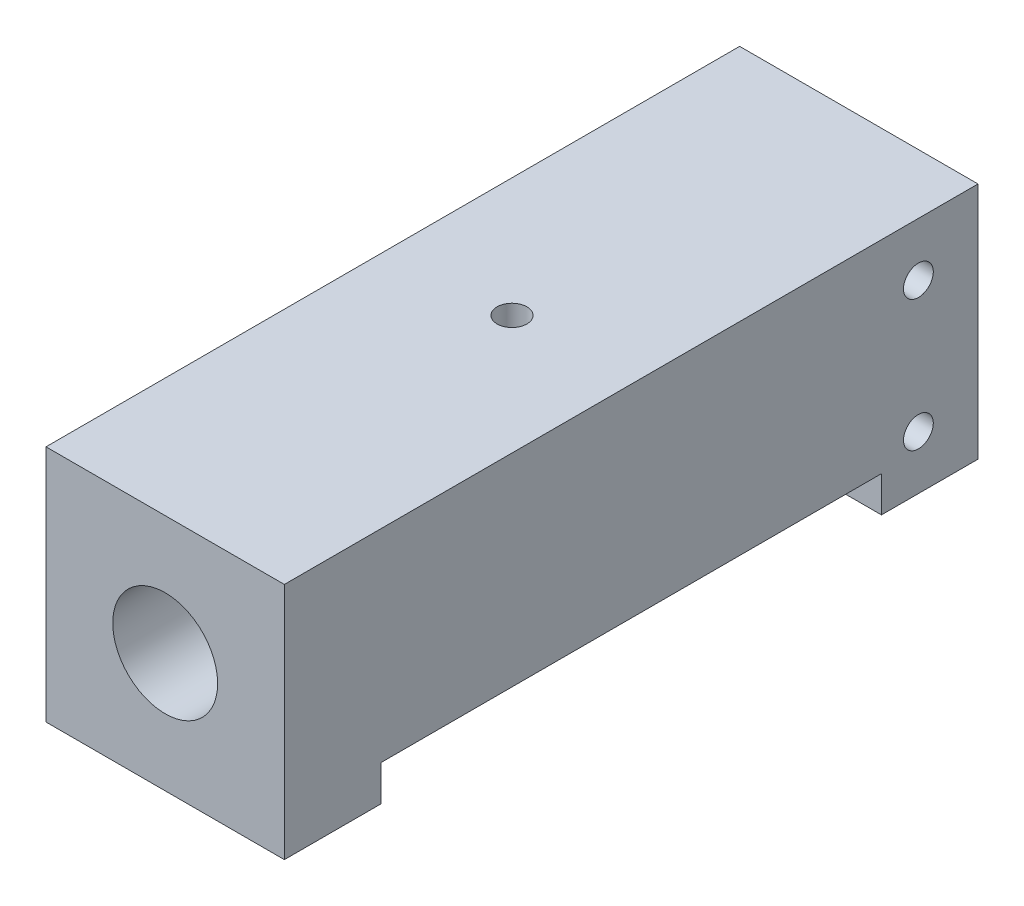
SolidWorks part; units mm, degrees
material "6063-T5"
ref_plane "Piano frontale" through (0, 0, 0) normal (0, 0, 1) x (1, 0, 0)
ref_plane "Piano superiore" through (0, 0, 0) normal (0, 1, 0) x (1, 0, 0)
ref_plane "Piano destro" through (0, 0, 0) normal (1, 0, 0) x (0, 0, -1)
sketch "Schizzo1" plane through (0, 0, 0) normal (0, 0, 1) x (1, 0, 0)
  line L1 (10, -10) -> (-10, -10)
  line L2 (10, -10) -> (10, 10)
  line L3 (10, 10) -> (-10, 10)
  line L4 (-10, -10) -> (-10, 10)
  line L5 (10, -10) -> (-10, 10) construction
  line L6 (10, 10) -> (-10, -10) construction
  point P0 (0, 0)
  dimension "D1" = 20
  dimension "D2" = 20
extrude "Estrusione-Estrusione1" add sketch "Schizzo1" against normal blind 58.2
sketch "Schizzo2" plane through (0, 0, -58.2) normal (0, 0, -1) x (-1, 0, 0)
  circle A0 centre (0, 0) radius 2.05
  dimension "D1" = 4.1
extrude "Taglio-Estrusione1" cut sketch "Schizzo2" against normal through all
sketch "Schizzo3" plane through (0, 0, -58.2) normal (0, 0, -1) x (-1, 0, 0)
  point P0 (0, 0)
hole_wizard "Foro filettato G1/8-1" positions "Schizzo8" profile "Schizzo7" tap size "G1/8" standard "BSI"
sketch "Schizzo8" plane through (0, 0, 0) normal (0, 0, 1) x (1, 0, 0)
  point P0 (0, 0)
sketch "Schizzo7" plane through (0, 0, 0) normal (1, 0, 0) x (0, -1, 0)
  line L0 (0, 0) -> (0, 12.6438)
  line L1 (0, 12.6438) -> (4.4, 10)
  line L2 (4.4, 10) -> (4.4, 0)
  line L5 (4.4, 0) -> (0, 0)
  line L10 (0, 12.6438) -> (-4.4, 10) construction
  line L11 (0, -6.35) -> (0, 107.95) construction
  dimension "Tap Drill Dia." = 8.8
  dimension "Tap Drill Depth" = 10
  dimension "Drill Angle" = 118
sketch "Schizzo11" plane through (0, 10, 0) normal (0, 1, 0) x (1, 0, 0)
  line L0 (0, 58.2) -> (0, 0) construction
  line L1 (10, 58.2) -> (-10, 58.2) construction
  line L2 (10, 29.1) -> (-10, 29.1) construction
  line L3 (10, 58.2) -> (10, 0) construction
  point P10 (0, 29.1)
  point P11 (0, 29.1)
  point P12 (0, 29.1)
hole_wizard "M3 Tapped Hole2" positions "Schizzo3D1" profile "Schizzo12" tap size "M3" standard "DIN"
sketch3d "Schizzo3D1"
  point P0 (0, 10, -29.1)
sketch "Schizzo12" plane through (0, 10, -29.1) normal (1, 0, 0) x (0, 0, 1)
  line L0 (0, 0) -> (0, 5.7511)
  line L1 (0, 5.7511) -> (1.25, 5)
  line L2 (1.25, 5) -> (1.25, 0)
  line L5 (1.25, 0) -> (0, 0)
  line L10 (0, 5.7511) -> (-1.25, 5) construction
  line L11 (0, -6.35) -> (0, 107.95) construction
  dimension "Tap Drill Dia." = 2.5
  dimension "Tap Drill Depth" = 5
  dimension "Drill Angle" = 118
cosmetic thread "Hole Thread4" parameters "D1"=5, "D2"=3
hole_wizard "Foro Ø16.0 (16)-1" positions "Schizzo3D3" profile "Schizzo14" hole size "Ø16.0" standard "ISO"
sketch3d "Schizzo3D3"
  point P0 (0, 0, 0)
  point P3 (0, 0, -58.2)
sketch "Schizzo14" plane through (0, 0, -58.2) normal (1, 0, 0) x (0, 1, 0)
  line L0 (0, 0) -> (0, 16.8069)
  line L1 (0, 16.8069) -> (8, 12)
  line L2 (8, 12) -> (8, 0)
  line L5 (8, 0) -> (0, 0)
  line L10 (0, 16.8069) -> (-8, 12) construction
  line L11 (0, -6.35) -> (0, 107.95) construction
  dimension "Hole Dia." = 16
  dimension "Hole Depth" = 12
  dimension "Drill Angle" = 118
sketch "Schizzo15" plane through (10, 0, 0) normal (1, 0, 0) x (0, 0, -1)
  line L0 (46.2, 0) -> (58.2, 0) construction
  line L1 (46.2, 8) -> (46.2, -8) construction
  line L4 (58.2, -10) -> (58.2, 10) construction
  line L6 (58.2, -10) -> (0, -10) construction
  point P5 (53.2, -5.5)
  point P8 (53.2, 5.5)
  dimension "D1" = 5.5
  dimension "D2" = 7
  dimension "D3" = 5
  dimension "D4" = 4.5
hole_wizard "M3 Tapped Hole3" positions "Schizzo3D4" profile "Schizzo16" tap size "M3" standard "ISO" end condition up to next
sketch3d "Schizzo3D4"
  point P0 (10, 5.5, -53.2)
  point P3 (10, -5.5, -53.2)
sketch "Schizzo16" plane through (10, 5.5, -53.2) normal (0, 1, 0) x (0, 0, -1)
  line L0 (0, 0) -> (0, 4.1905)
  line L1 (0, 4.1905) -> (1.25, 4.1905)
  line L2 (1.25, 4.1905) -> (1.25, 0)
  line L5 (1.25, 0) -> (0, 0)
  line L11 (0, -6.35) -> (0, 107.95) construction
  dimension "Thread Major Dia." = 2.5
  dimension "Thru Tap Drill Depth" = 4.1905
sketch "Sketch1" plane through (-10, 0, 0) normal (-1, 0, 0) x (0, 0, 1)
  line L0 (-58.2, 10) -> (-58.2, -10) construction
  line L1 (-58.2, 3) -> (-22, 3)
  line L2 (-58.2, 3) -> (-58.2, -3)
  line L3 (-58.2, -3) -> (-22, -3)
  line L4 (-22, 3) -> (-22, -3)
  line L5 (0, 10) -> (0, -10) construction
  line L6 (0, 0) -> (-22, 0) construction
  point P8 (-22, 0)
  dimension "D1" = 6
  dimension "D2" = 22
extrude "Boss-Extrude1" add sketch "Sketch1" along normal blind 4.9
sketch "Sketch2" plane through (10, 0, 0) normal (1, 0, 0) x (0, 0, -1)
  line L0 (58.2, -10) -> (0, -10) construction
  line L1 (50.1, -10) -> (34.1, -10)
  line L2 (50.1, -10) -> (50.1, -7)
  line L3 (50.1, -7) -> (34.1, -7)
  line L4 (34.1, -7) -> (8.1, -7)
  line L5 (42.1, -7) -> (42.1, -12.5) construction
  line L6 (8.1, -7) -> (8.1, -10)
  line L7 (8.1, -10) -> (34.1, -10)
  line L8 (0, -10) -> (8.1, -10) construction
  line L9 (50.1, -10) -> (58.2, -10) construction
  dimension "D1" = 16
  dimension "D2" = 3
extrude "Cut-Extrude1" cut sketch "Sketch2" against normal through all
sketch "Sketch3" plane through (0, 0, -22) normal (0, 0, 1) x (1, 0, 0)
  point P0 (-13, 0)
hole_wizard "M3 Tapped Hole4" positions "Sketch6" profile "Sketch7" tap size "M3" standard "ISO"
sketch "Sketch6" plane through (0, 0, -22) normal (0, 0, 1) x (1, 0, 0)
  point P0 (-13, 0)
sketch "Sketch7" plane through (-13, 0, -22) normal (1, 0, 0) x (0, -1, 0)
  line L0 (0, 0) -> (0, 20.7511)
  line L1 (0, 20.7511) -> (1.25, 20)
  line L2 (1.25, 20) -> (1.25, 0)
  line L5 (1.25, 0) -> (0, 0)
  line L10 (0, 20.7511) -> (-1.25, 20) construction
  line L11 (0, -6.35) -> (0, 107.95) construction
  dimension "Tap Drill Dia." = 2.5
  dimension "Tap Drill Depth" = 20
  dimension "Drill Angle" = 118
sketch "Sketch8" plane through (-10, 0, 0) normal (-1, 0, 0) x (0, 0, 1)
  line L1 (0, 10) -> (-58.2, 10) construction
  line L2 (0, 10) -> (0, -10) construction
  line L3 (0, -10) -> (-58.2, -10) construction
  line L4 (-58.2, 10) -> (-58.2, -10) construction
sketch "Sketch9" plane through (0, -10, 0) normal (0, -1, 0) x (1, 0, 0)
  line L1 (14, -8.1) -> (-14, -8.1) construction
  line L2 (14, -8.1) -> (14, -50.1) construction
  line L3 (14, -50.1) -> (-14, -50.1) construction
  line L4 (-14, -8.1) -> (-14, -50.1) construction
  line L6 (-10, -50.1) -> (-3.873, -50.1) construction
  line L7 (-10, -8.1) -> (10, -8.1) construction
  line L8 (10, -50.1) -> (10, -8.1) construction
  line L9 (-10, 0) -> (-10, -58.2) construction
  dimension "D1" = 4
  dimension "D2" = 4
